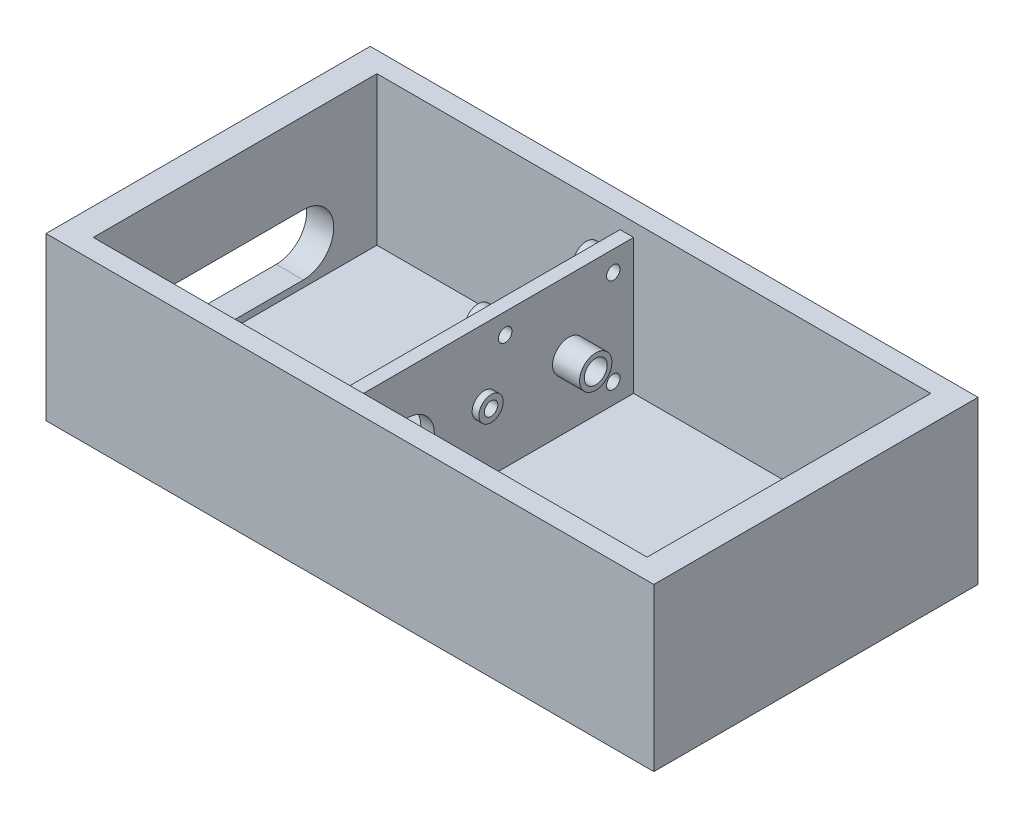
SolidWorks part; units mm, degrees
ref_plane "前视基准面" through (0, 0, 0) normal (0, 0, 1) x (1, 0, 0)
ref_plane "上视基准面" through (0, 0, 0) normal (0, 1, 0) x (1, 0, 0)
ref_plane "右视基准面" through (0, 0, 0) normal (1, 0, 0) x (0, 0, -1)
sketch "草图2" plane through (0, 0, 0) normal (1, 0, 0) x (0, 0, -1)
  line L1 (-12, 6) -> (12, 6)
  line L2 (-12, 6) -> (-12, -6)
  line L3 (-12, -6) -> (12, -6)
  line L4 (12, 6) -> (12, -6)
  line L5 (-12, 6) -> (12, -6) construction
  line L6 (-12, -6) -> (12, 6) construction
  point P0 (0, 0)
  dimension "D1" = 12
  dimension "D2" = 24
extrude "凸台-拉伸1" add sketch "草图2" along normal blind 45
sketch "草图3" plane through (0, 6, 0) normal (0, 1, 0) x (1, 0, 0)
  line L0 (0, 12) -> (0, -12) construction
  line L1 (2, 10.5) -> (43, 10.5)
  line L2 (2, 10.5) -> (2, -10.5)
  line L3 (2, -10.5) -> (43, -10.5)
  line L4 (43, 10.5) -> (43, -10.5)
  line L5 (45, 12) -> (0, 12) construction
  line L6 (45, 12) -> (45, -12) construction
  line L7 (45, -12) -> (0, -12) construction
  dimension "D1" = 2
  dimension "D2" = 1.5
  dimension "D3" = 2
  dimension "D4" = 1.5
extrude "切除-拉伸1" cut sketch "草图3" against normal blind 11
sketch "草图4" plane through (0, 0, 0) normal (-1, 0, 0) x (0, 0, 1)
  line L0 (-5.05, -2.25) -> (6.45, -2.25) construction
  line L1 (-5.05, 0) -> (6.45, 0)
  line L2 (-5.05, -4.5) -> (6.45, -4.5)
  line L6 (12, 6) -> (12, -6) construction
  line L7 (-12, 6) -> (12, 6) construction
  arc A0 (-5.05, 0) -> (-5.05, -4.5) centre (-5.05, -2.25) ccw
  arc A1 (6.45, -4.5) -> (6.45, 0) centre (6.45, -2.25) ccw
  point P2 (0.7, -2.25)
  point P7 (8.7, -2.25)
  point P8 (-7.3, -2.25)
  dimension "D2" = 16
  dimension "D1" = 11.5
  dimension "D3" = 3.3
  dimension "D4" = 6
extrude "切除-拉伸2" cut sketch "草图4" against normal blind 2
sketch "草图7" plane through (0, -5, 0) normal (0, 1, 0) x (1, 0, 0)
  line L0 (43, 10.5) -> (2, 10.5) construction
  line L1 (20, 10.5) -> (21, 10.5)
  line L2 (20, 10.5) -> (20, -10.5)
  line L3 (20, -10.5) -> (21, -10.5)
  line L4 (21, 10.5) -> (21, -10.5)
  line L5 (2, -10.5) -> (43, -10.5) construction
  line L6 (2, 10.5) -> (2, -10.5) construction
  dimension "D1" = 18
  dimension "D2" = 1
extrude "凸台-拉伸4" add sketch "草图7" along normal blind 10
sketch "草图8" plane through (20, 0, 0) normal (-1, 0, 0) x (0, 0, 1)
  line L1 (12, -6) -> (-12, -6) construction
  line L2 (-12, -6) -> (-12, 6) construction
  circle A0 centre (-5.7, -0.2) radius 0.85
  dimension "D3" = 1.7
  dimension "D1" = 5.8
  dimension "D2" = 6.3
extrude "切除-拉伸3" cut sketch "草图8" against normal blind 3
sketch "草图9" plane through (21, 0, 0) normal (1, 0, 0) x (0, 0, -1)
  circle A0 centre (5.7, -0.2) radius 1.2
  dimension "D1" = 2.4
extrude "凸台-拉伸5" add sketch "草图9" along normal blind 2
sketch "草图10" plane through (23, 0, 0) normal (1, 0, 0) x (0, 0, -1)
  circle A0 centre (5.7, -0.2) radius 0.85
  dimension "D1" = 1.7
extrude "切除-拉伸4" cut sketch "草图10" against normal blind 2
sketch "草图11" plane through (21, 0, 0) normal (1, 0, 0) x (0, 0, -1)
  line L0 (-10.5, -5) -> (10.5, -5) construction
  circle A0 centre (-0.55, -0.2) radius 0.9
  circle A1 centre (5.7, -0.2) radius 1.2 construction
  dimension "D1" = 1.8
  dimension "D2" = 6.25
  dimension "D3" = 4.8
extrude "凸台-拉伸6" add sketch "草图11" along normal blind 0.5
sketch "草图12" plane through (21.5, 0, 0) normal (1, 0, 0) x (0, 0, -1)
  circle A0 centre (-0.55, -0.2) radius 0.5
  dimension "D1" = 1
extrude "切除-拉伸5" cut sketch "草图12" against normal blind 2 and the other way blind 17
sketch "草图13" plane through (21, 0, 0) normal (1, 0, 0) x (0, 0, -1)
  line L0 (-10.5, -5) -> (10.5, -5) construction
  circle A0 centre (-6.25, -0.2) radius 2
  circle A1 centre (-0.55, -0.2) radius 0.9 construction
  dimension "D1" = 4
  dimension "D2" = 5.7
  dimension "D3" = 4.8
extrude "切除-拉伸6" cut sketch "草图13" against normal blind 2
sketch "草图14" plane through (21, 0, 0) normal (1, 0, 0) x (0, 0, -1)
  line L0 (-10.5, -5) -> (10.5, -5) construction
  line L1 (10.5, 5) -> (10.5, -5) construction
  line L2 (-10.5, 5) -> (10.5, 5) construction
  circle A0 centre (9, -3.5) radius 0.5
  circle A1 centre (9, 3.5) radius 0.5
  circle A2 centre (1, 3.5) radius 0.5
  dimension "D1" = 1
  dimension "D4" = 1
  dimension "D7" = 1
  dimension "D2" = 1.5
  dimension "D3" = 1.5
  dimension "D5" = 1.5
  dimension "D6" = 1.5
  dimension "D8" = 8
  dimension "D9" = 1.5
extrude "切除-拉伸7" cut sketch "草图14" against normal blind 2
sketch "草图16" plane through (20, 0, 0) normal (-1, 0, 0) x (0, 0, 1)
  circle A0 centre (-9, 3.5) radius 1
  circle A1 centre (-1, 3.5) radius 1
  circle A2 centre (-9, -3.5) radius 1
  dimension "D1" = 2
  dimension "D2" = 2
  dimension "D3" = 2
extrude "凸台-拉伸7" add sketch "草图16" along normal blind 1
sketch "草图17" plane through (19, 0, 0) normal (-1, 0, 0) x (0, 0, 1)
  circle A0 centre (-9, 3.5) radius 0.5
  circle A1 centre (-1, 3.5) radius 0.5
  circle A2 centre (-9, -3.5) radius 0.5
  dimension "D1" = 1
  dimension "D2" = 1
  dimension "D3" = 1
extrude "切除-拉伸8" cut sketch "草图17" against normal blind 1
sketch "草图18" plane through (20, 0, 0) normal (-1, 0, 0) x (0, 0, 1)
  circle A0 centre (0.55, -0.2) radius 1
  dimension "D1" = 2
extrude "凸台-拉伸8" add sketch "草图18" along normal blind 1
sketch "草图20" plane through (20, 0, 0) normal (1, 0, 0) x (0, 0, -1)
  circle A0 centre (-0.55, -0.2) radius 0.5
extrude "切除-拉伸14" cut sketch "草图20" against normal blind 0.5
